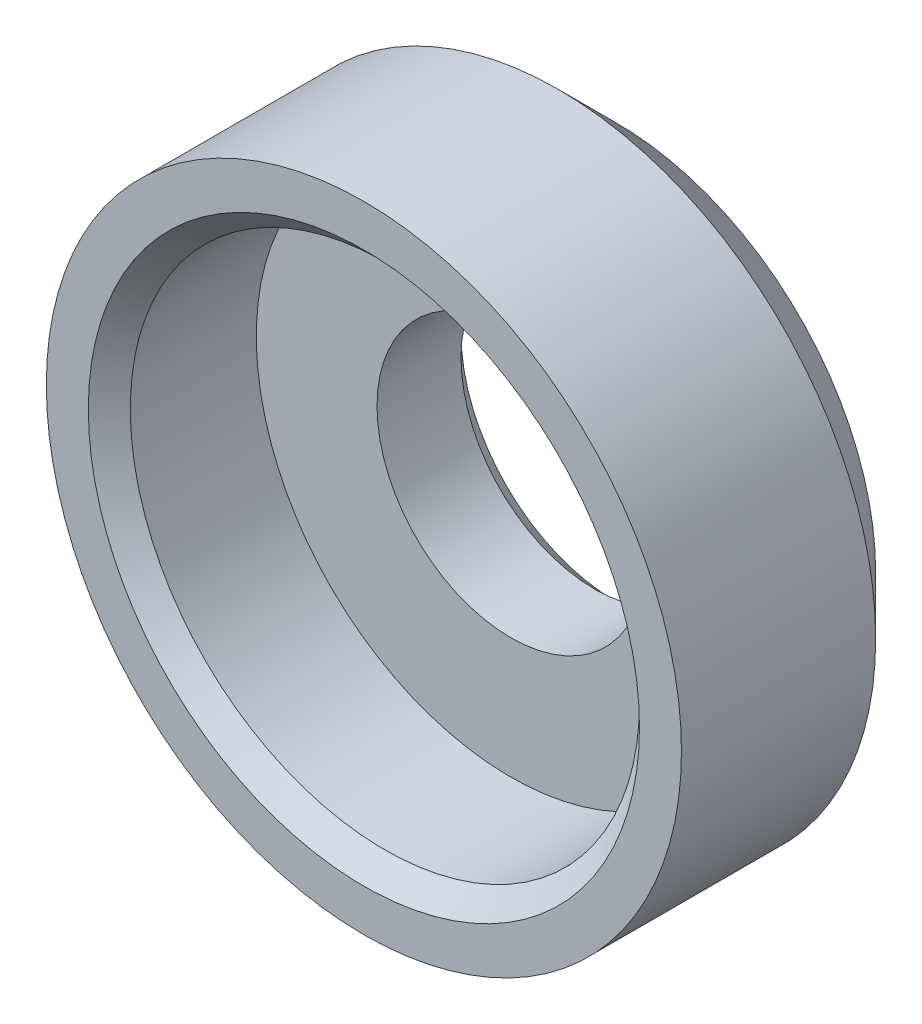
SolidWorks part; units mm, degrees
material "ABS"
ref_plane "Plan de face" through (0, 0, 0) normal (0, 0, 1) x (1, 0, 0)
ref_plane "Plan de dessus" through (0, 0, 0) normal (0, 1, 0) x (1, 0, 0)
ref_plane "Plan de droite" through (0, 0, 0) normal (1, 0, 0) x (0, 0, -1)
sketch "Esquisse1" plane through (0, 0, 0) normal (0, 0, 1) x (1, 0, 0)
  circle A0 centre (0, 0) radius 2.55
  circle A1 centre (0, 0) radius 4.95
  dimension "D1" = 5.1
  dimension "D2" = 2.4
extrude "Boss.-Extru.1" add sketch "Esquisse1" along normal blind 2
sketch "Esquisse2" plane through (0, 0, 2) normal (0, 0, 1) x (1, 0, 0)
  circle A0 centre (0, 0) radius 6.05
  circle A1 centre (0, 0) radius 4.85
  dimension "D1" = 9.7
  dimension "D2" = 1.2
extrude "Boss.-Extru.2" add sketch "Esquisse2" along normal blind 2.8
chamfer "Chanfrein1" distance 2 angle 45 1 edges at (4.95, 0, 2)
chamfer "Chanfrein2" distance 0.4 angle 45 2 edges at (2.55, 0, 0) (4.85, 0, 4.8)
